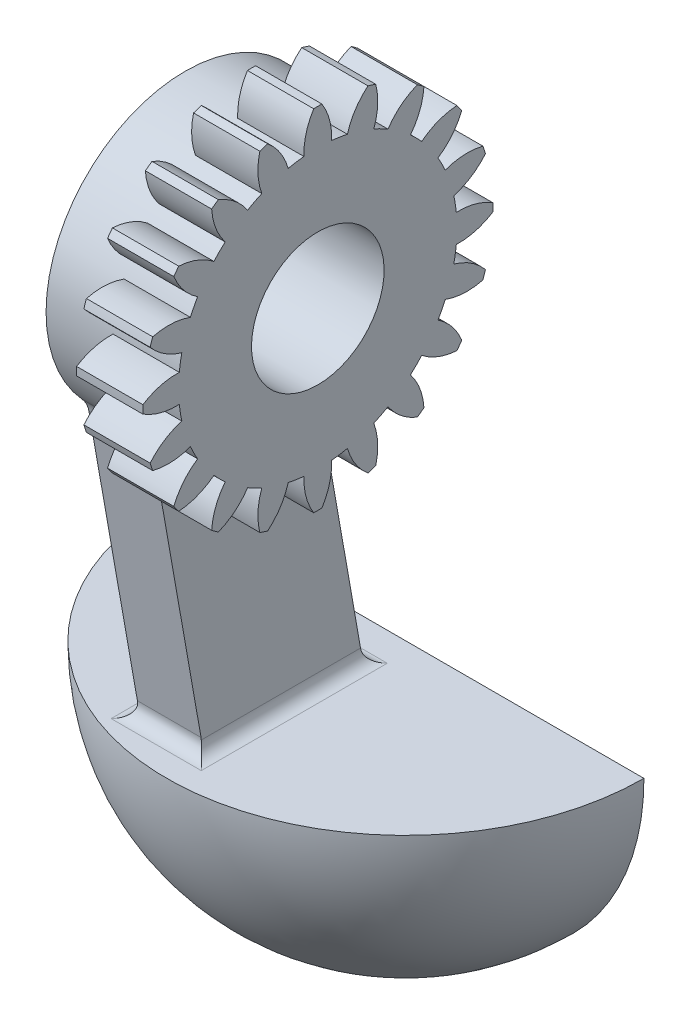
SolidWorks part; units mm, degrees
note: '?' marks a value the reader was unsure of.
ref_plane "Plane1" through (0, 0, 0) normal (0, 0, 1) x (1, 0, 0)
ref_plane "Plane2" through (0, 0, 0) normal (0, 1, 0) x (1, 0, 0)
ref_plane "Plane3" through (0, 0, 0) normal (1, 0, 0) x (0, 0, -1)
other "Configuration Table"
sketch "HoldingSke" plane through (0, 0, 0) normal (0, 1, 0) x (1, 0, 0)
  line L0 (0, 0) -> (1.5662, -0.57)
  line L1 (-15, 0) -> (100, 0) construction
  line L2 (0, 0) -> (-2.1039, 2.3779)
  line L3 (0, 0) -> (-11.863, 4.5341)
  line L4 (0, 0) -> (8.1152, 2.9537)
  line L5 (0, 0) -> (-4.6848, -1.7473)
  line L6 (0, 0) -> (-2.0724, -1.3983)
  line L7 (-2.1039, 2.3779) -> (-1.0276, 7.2607)
  line L8 (-76.2, 54.61) -> (-75.3, 54.61)
  line L9 (-71.009, 38.7566) -> (-53.1078, 45.2721)
  line L10 (-76.2, 71.12) -> (104.1128, 71.12)
  line L11 (0, 0) -> (-2.5, 0)
  line L12 (-76.2, 101.6) -> (-76.177, 101.6)
  line L13 (24.9733, 27.94) -> (52.9518, 28.4284)
  line L14 (24.9733, 27.94) -> (24.9743, 27.94)
  line L15 (24.9733, 27.94) -> (100.4006, 29.5858)
  line L16 (-63.627, -0.6) -> (-12.827, -0.6)
  circle A0 centre (0, 0) radius 2.5
  circle A1 centre (0, 0) radius 5.249
  circle A2 centre (0, 0) radius 10
  circle A3 centre (0, 0) radius 2.5
  dimension "Num_teeth" = 20
  dimension "Pitch_radius" = 180.3128
  dimension "Width" = 2.5
  dimension "Thickness" = 2.5
sketch "BasProSke" plane through (0, 0, 0) normal (0, 1, 0) x (1, 0, 0)
  line L0 (-10, 0) -> (60, 0) construction
  line L1 (0, 0) -> (0, 6.6)
  line L2 (0, 0) -> (2.5, 0)
  line L3 (2.5, 0) -> (2.5, 6.6)
  line L4 (2.5, 6.6) -> (0, 6.6)
  dimension "Thickness" = 2.5
  dimension "Diameter" = 13.2
revolve "Base-Revolve" add sketch "BasProSke" angle 360 about L0
sketch "TooCutSke" plane through (0, 0, 0) normal (1, 0, 0) x (0, 0, -1)
  line L1 (0, 0) -> (0, 107) construction
  line L2 (0, 0) -> (-0.511, 5.9782) construction
  line L3 (0, 0) -> (-1.8724, 11.8217) construction
  line L4 (-0.511, 5.9782) -> (-0.9362, 5.9109) construction
  arc A0 (0.3002, 5.2404) -> (-0.3002, 5.2404) centre (0, 0) ccw
  arc A1 (0.8997, 6.564) -> (-0.8997, 6.564) centre (0, 0) ccw
  circle A2 centre (0, 0) radius 6 construction
  circle A3 centre (0, 0) radius 5.6382 construction
  arc A4 (-0.3002, 5.2404) -> (-0.8997, 6.564) centre (-2.6836, 4.9585) ccw
  arc A5 (0.8997, 6.564) -> (0.3002, 5.2404) centre (2.6836, 4.9585) ccw
extrude "ToothCut" cut sketch "TooCutSke" along normal through all
fillet "Breaks" [suppressed] radius 0.012
fillet "RootFillets" [suppressed] radius 0.151
pattern_circular "TeethCuts" count 20 every 18 about axis through (-10, 0, 0) along (1, 0, 0) of "ToothCut", "RootFillets", "Breaks"
sketch "HubNeaOneSke" plane through (0, 0, 0) normal (-1, 0, 0) x (0, 0, 1)
  circle A0 centre (0, 0) radius 5.249
  dimension "Diameter" = 10.498
extrude "HubNearOne" add sketch "HubNeaOneSke" along normal blind 2.5001
sketch "HubNeaBotSke" plane through (0, 0, 0) normal (-1, 0, 0) x (0, 0, 1)
  circle A0 centre (0, 0) radius 5.249
  dimension "Diameter" = 10.498
extrude "HubNearBoth" [suppressed] add sketch "HubNeaBotSke" along normal blind 1.25
ref_plane "FarPln" through (2.5, 0, 0) normal (1, 0, 0) x (0, 0, -1)
sketch "HubFarSke" plane through (2.5, 0, 0) normal (1, 0, 0) x (0, 0, -1)
  circle A0 centre (0, 0) radius 5.249
  dimension "Diameter" = 10.498
extrude "HubFar" [suppressed] add sketch "HubFarSke" along normal blind 1.25
sketch "BorSke" plane through (0, 0, 0) normal (1, 0, 0) x (0, 0, -1)
  circle A0 centre (0, 0) radius 2.5
  dimension "Diameter" = 5
extrude "Bore" cut sketch "BorSke" along normal mid plane 10.0001
sketch "KeySke" plane through (0, 0, 0) normal (1, 0, 0) x (0, 0, -1)
  line L0 (-1, 0) -> (-1, 3.4)
  line L1 (-1, 3.4) -> (1, 3.4)
  line L2 (1, 3.4) -> (1, 0)
  line L3 (0, 0) -> (0, 34) construction
  line L4 (-1, 0) -> (1, 0)
  dimension "Width" = 2
extrude "Keyway" [suppressed] cut sketch "KeySke" along normal mid plane 10.0001
pattern_circular "Keyway2" [suppressed] count 2 every 90 about axis through (-10, 0, 0) along (1, 0, 0)
ref_axis "基准轴2" through (2.5, 0, 0) along (-1, 0, 0)?
move or copy body "实体-移动/复制1" bodies to move or copy 103 copy no rotation origin (0, 0, 0) rotation axis (-1, 0, 0) rotation angle 9
ref_plane "基准面1" through (0, 0, -5.8) normal (0, 0, 1) x (1, 0, 0)
ref_plane "基准面2" through (0, -15, 0) normal (0, 1, 0) x (1, 0, 0)
sketch "草图4" plane through (0, -5.8007, 0.6057) normal (1, 0, 0) x (0, 0, -1)
  line L0 (6.4057, -9.1993) -> (6.4057, -18.1993)
  line L1 (6.4057, -9.1993) -> (6.4057, -18.1993)
  line L2 (6.4057, -9.1993) -> (-2.5943, -9.1993)
  line L3 (50.6057, -9.1993) -> (-49.3943, -9.1993) construction
  line L4 (6.4057, 55.8007) -> (6.4057, -44.1993) construction
  arc A0 (-2.5943, -9.1993) -> (6.4057, -18.1993) centre (6.4057, -9.1993) ccw
  dimension "D1" = 9
revolve "旋转1" add sketch "草图4" angle 90 about L0
sketch "草图5" plane through (-2.5001, 0, 0) normal (-1, 0, 0) x (0, 0, 1)
  line L15 (-4.3, -15) -> (-2.3847, -4.1376)
  line L22 (3.2, -15) -> (-5.8, -15) construction
  line L23 (-5.8, -15) -> (-5.8, -24) construction
  line L24 (-4.3, -15) -> (1.7, -15)
  line L25 (1.7, -15) -> (3.8456, -2.8316)
  arc A1 (-2.3847, -4.1376) -> (3.8456, -2.8316) centre (0, 0) ccw
  dimension "D1" = 100
  dimension "D2" = 1.5
  dimension "D3" = 6
extrude "凸台-拉伸1" add sketch "草图5" against normal blind 2.4
fillet "圆角1" radius 1 2 edges at (-1.3001, -3.7371, 3.686) (-1.3001, -4.6307, -2.4716)
fillet "圆角2" radius 0.5 4 edges at (-0.1001, -15, -1.3) (-1.3001, -15, -4.3) (-1.3001, -15, 1.7) (-2.5001, -15, -1.3)
equation "' \"Module@HoldingSke\" = 6.35"
equation "' \"Num_teeth@HoldingSke\" = 12"
equation "' \"Ap@HoldingSke\" =  20"
equation "' \"Ap@HoldingSke\" = 20"
equation "' \"Width@HoldingSke\" = 0.5 * 25.4"
equation "' \"Hub_dia@HoldingSke\"= 1 * 25.4"
equation "' \"Hub_dia@HoldingSke\" = 1 * 25.4"
equation "' \"Overall_len@HoldingSke\" = 1.0 * 25.4"
equation "' \"Bore@HoldingSke\" = 0.75 * 25.4"
equation "' \"T_dim@HoldingSke\" = 0.1 * 25.4"
equation "' \"Width@KeySke\" = 0.25 * 25.4"
equation "' \"Show_teeth@HoldingSke\" = 13"
equation "' \"Backlash@HoldingSke\" = 0.009 * 25.4"
equation "' \"Addendum_fac@HoldingSke\" = 1.0"
equation "' \"Dedendum_fac@HoldingSke\" = 1.25"
equation "' \"Dedendum_add@HoldingSke\" = 0.00005 * 25.4"
equation "' \"Clearance_fac@HoldingSke\" = 0.25"
equation "\"Pitch@HoldingSke\" = 1 / \"Module@HoldingSke\""
equation "\"Overcut_dia@TooCutSke\" = (\"Num_teeth@HoldingSke\" + 2 * \"Addendum_fac@HoldingSke\") / \"Pitch@HoldingSke\" + 0.002 * 25.4"
equation "\"Pitch_dia@TooCutSke\" = \"Num_teeth@HoldingSke\" / \"Pitch@HoldingSke\""
equation "\"Base_dia@TooCutSke\" = \"Num_teeth@HoldingSke\" / \"Pitch@HoldingSke\" * cos((\"Ap@HoldingSke\"  * 3.14159265 / 180))"
equation "\"Root_dia@TooCutSke\" = (\"Num_teeth@HoldingSke\" + 2) / \"Pitch@HoldingSke\" - 2 * (\"Addendum_fac@HoldingSke\" + \"Dedendum_fac@HoldingSke\") / \"Pitch@HoldingSke\" - \"Dedendum_add@HoldingSke\" * 2"
equation "\"Half_ang@TooCutSke\" = 180 / \"Num_teeth@HoldingSke\""
equation "\"Half_CT@TooCutSke\" = \"Num_teeth@HoldingSke\" / \"Pitch@HoldingSke\" * sin((3.14159265 / 2 / \"Num_teeth@HoldingSke\")) / 2 - 7 * \"Backlash@HoldingSke\" / 4"
equation "\"Flank_rad@TooCutSke\" = \"Num_teeth@HoldingSke\" / \"Pitch@HoldingSke\" / 5"
equation "\"Radius@RootFillets\" = \"Clearance_fac@HoldingSke\" / \"Pitch@HoldingSke\" + \"Dedendum_add@HoldingSke\""
equation "\"Break_rad@Breaks\" = 0.02 / \"Pitch@HoldingSke\""
equation "\"Thickness@HoldingSke\" = \"Width@HoldingSke\""
equation "\"OAL@HoldingSke\" = \"Thickness@HoldingSke\""
equation "\"MHD@HoldingSke\" = (\"Num_teeth@HoldingSke\" + 2) / \"Pitch@HoldingSke\" - 2 * (\"Addendum_fac@HoldingSke\" + \"Dedendum_fac@HoldingSke\")  / \"Pitch@HoldingSke\" - \"Dedendum_add@HoldingSke\" * 2"
equation "\"MBD@HoldingSke\" = (\"Num_teeth@HoldingSke\" + 2) / \"Pitch@HoldingSke\" - 2 * (\"Addendum_fac@HoldingSke\" + \"Dedendum_fac@HoldingSke\")  / \"Pitch@HoldingSke\" - \"Dedendum_add@HoldingSke\" * 2 - 0.002 * 25.4"
equation "\"MHD@HoldingSke\" = ((sgn( \"MHD@HoldingSke\" - \"Hub_dia@HoldingSke\" )-1)*( \"MHD@HoldingSke\" - \"Hub_dia@HoldingSke\" ))/-2+ \"Hub_dia@HoldingSke\""
equation "\"MBD@HoldingSke\" = ((sgn( \"MBD@HoldingSke\" - \"Bore@HoldingSke\" )-1)*( \"MBD@HoldingSke\" - \"Bore@HoldingSke\" ))/-2+ \"Bore@HoldingSke\""
equation "\"OAL@HoldingSke\" = ((sgn( \"OAL@HoldingSke\" - \"Overall_len@HoldingSke\" )+1)*( \"OAL@HoldingSke\" - \"Overall_len@HoldingSke\" ))/2 + \"Overall_len@HoldingSke\" + 0.000002 * 25.4"
equation "\"Num_teeth@TeethCuts\" = int( \"Show_teeth@HoldingSke\" ) + 1"
equation "\"Num_teeth@TeethCuts\" = ((sgn( \"Num_teeth@TeethCuts\" - \"Num_teeth@HoldingSke\" )-1)*( \"Num_teeth@TeethCuts\" - \"Num_teeth@HoldingSke\" ))/-2+ \"Num_teeth@HoldingSke\""
equation "\"Num_teeth@TeethCuts\" = ((sgn( \"Num_teeth@TeethCuts\" - 2.0)+1)*( \"Num_teeth@TeethCuts\" - 2.0))/2 +2.0"
equation "\"Angle@TeethCuts\" = 360.0 / \"Num_teeth@HoldingSke\""
equation "\"Diameter@BasProSke\" = (\"Num_teeth@HoldingSke\" + 2 * \"Addendum_fac@HoldingSke\") / \"Pitch@HoldingSke\""
equation "\"Thickness@BasProSke\"  = \"Thickness@HoldingSke\""
equation "' \"Fillet_rad@BasProSke\" =  \"Thickness@HoldingSke\" * 0.05"
equation "' \"Fillet_rad@BasProSke\" = \"Thickness@HoldingSke\" * 0.05"
equation "\"MHD@HoldingSke\" = ((sgn( \"MHD@HoldingSke\" - \"Root_dia@TooCutSke\" )-1)*( \"MHD@HoldingSke\" - \"Root_dia@TooCutSke\" ))/-2+ \"Root_dia@TooCutSke\""
equation "\"Diameter@HubNeaOneSke\" = \"MHD@HoldingSke\""
equation "\"Length@HubNearOne\" = \"OAL@HoldingSke\" - \"Thickness@BasProSke\""
equation "\"Diameter@HubNeaBotSke\" = \"MHD@HoldingSke\""
equation "\"Length@HubNearBoth\" = ( \"OAL@HoldingSke\" - \"Thickness@BasProSke\" ) / 2.0"
equation "\"Thickness@FarPln\" = \"Thickness@BasProSke\""
equation "\"Diameter@HubFarSke\" = \"MHD@HoldingSke\""
equation "\"Length@HubFar\" = ( \"OAL@HoldingSke\" - \"Thickness@BasProSke\" ) / 2.0"
equation "\"Diameter@BorSke\" = \"MBD@HoldingSke\""
equation "\"D1@Bore\" = \"OAL@HoldingSke\" * 2.0"
equation "\"D1@Keyway\" = \"OAL@HoldingSke\" * 2.0"
equation "\"Offset@KeySke\" = \"T_dim@HoldingSke\" + \"MBD@HoldingSke\" / 2.0"
